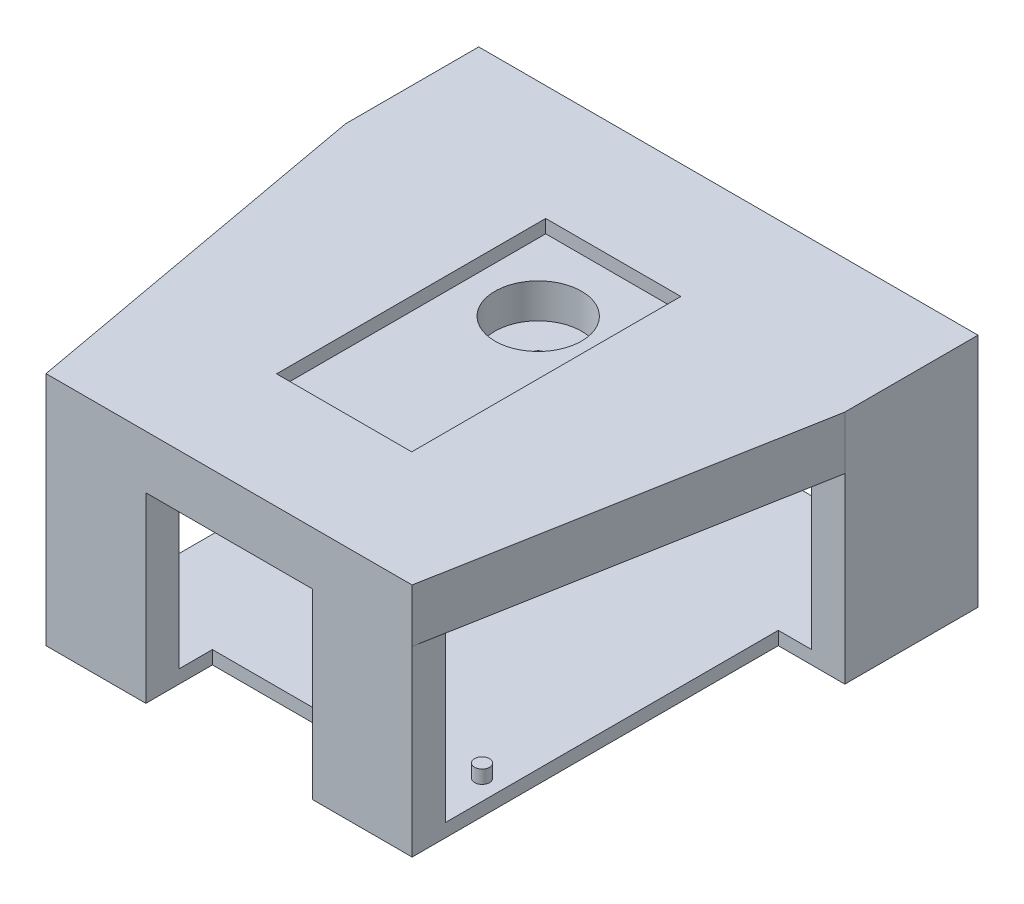
SolidWorks part; units mm, degrees
ref_plane "Front Plane" through (0, 0, 0) normal (0, 0, 1) x (1, 0, 0)
ref_plane "Top Plane" through (0, 0, 0) normal (0, 1, 0) x (1, 0, 0)
ref_plane "Right Plane" through (0, 0, 0) normal (1, 0, 0) x (0, 0, -1)
sketch "Sketch1" plane through (0, 0, 0) normal (0, 1, 0) x (1, 0, 0)
  line L1 (0, 0) -> (55, 0)
  line L2 (0, 0) -> (0, 65)
  line L3 (0, 65) -> (55, 65)
  line L4 (55, 0) -> (55, 65)
  dimension "D1" = 55
  dimension "D2" = 65
extrude "Base" add sketch "Sketch1" along normal blind 2
sketch "Sketch2" plane through (0, 2, 0) normal (0, 1, 0) x (1, 0, 0)
  line L0 (0, 0) -> (55, 0) construction
  line L2 (55, 65) -> (0, 65) construction
  circle A0 centre (3, 3.5) radius 1.125
  circle A1 centre (52, 3.5) radius 1.125
  circle A2 centre (3, 61.5) radius 1.125
  circle A3 centre (52, 61.5) radius 1.125
  point P8 (0, 0)
  point P9 (0, 0)
  point P12 (27.5, 0)
  point P13 (52, 2.848)
  dimension "D1" = 2.25
  dimension "D2" = 24.5
  dimension "D3" = 24.5
  dimension "D4" = 58
  dimension "D5" = 3.5
extrude "PiMountPegs" add sketch "Sketch2" along normal blind 2
sketch "Sketch3" plane through (0, 0, 0) normal (-1, 0, 0) x (0, 0, 1)
  line L0 (-65, 0) -> (0, 0) construction
  line L1 (-65, 2) -> (-45, 2)
  line L2 (-65, 2) -> (-65, 0)
  line L3 (-65, 0) -> (-45, 0)
  line L4 (-45, 2) -> (-45, 0)
  dimension "D1" = 20
extrude "ServoPlateLegExt-1" add sketch "Sketch3" along normal blind 10
sketch "Sketch4" plane through (55, 0, 0) normal (1, 0, 0) x (0, 0, -1)
  line L0 (0, 0) -> (65, 0) construction
  line L1 (65, 2) -> (45, 2)
  line L2 (65, 2) -> (65, 0)
  line L3 (65, 0) -> (45, 0)
  line L4 (45, 2) -> (45, 0)
  dimension "D1" = 20
extrude "ServoPlateLegExt-2" add sketch "Sketch4" along normal blind 10
sketch "Sketch5" plane through (0, 0, 0) normal (0, 0, 1) x (1, 0, 0)
  line L0 (0, 0) -> (55, 0) construction
  line L1 (0, 2) -> (15, 2)
  line L2 (0, 2) -> (0, 0)
  line L3 (0, 0) -> (15, 0)
  line L4 (15, 2) -> (15, 0)
  line L6 (55, 2) -> (40, 2)
  line L7 (55, 2) -> (55, 0)
  line L8 (55, 0) -> (40, 0)
  line L9 (40, 2) -> (40, 0)
  dimension "D1" = 15
  dimension "D2" = 15
extrude "ServoPlateLegExt-3" add sketch "Sketch5" along normal blind 10
sketch "Sketch6" plane through (0, 2, 0) normal (0, 1, 0) x (1, 0, 0)
  line L0 (-10, 45) -> (0, 45) construction
  line L1 (-10, 65) -> (-5, 65)
  line L2 (-10, 65) -> (-10, 45)
  line L3 (-10, 45) -> (-5, 45)
  line L4 (-5, 65) -> (-5, 45)
  line L5 (15, -10) -> (15, 0) construction
  line L6 (0, -10) -> (15, -10)
  line L7 (0, -10) -> (0, -5)
  line L8 (0, -5) -> (15, -5)
  line L9 (15, -10) -> (15, -5)
  line L10 (40, -10) -> (40, 0) construction
  line L11 (55, -10) -> (40, -10)
  line L12 (55, -10) -> (55, -5)
  line L13 (55, -5) -> (40, -5)
  line L14 (40, -10) -> (40, -5)
  line L15 (65, 45) -> (55, 45) construction
  line L16 (65, 65) -> (60, 65)
  line L17 (65, 65) -> (65, 45)
  line L18 (65, 45) -> (60, 45)
  line L19 (60, 65) -> (60, 45)
extrude "ServoLegs" add sketch "Sketch6" along normal blind 25.4
sketch "Sketch11" plane through (0, 27.4, 0) normal (0, 1, 0) x (1, 0, 0)
  line L0 (55, -10) -> (65, 45)
  line L1 (65, 45) -> (65, 65)
  line L2 (65, 65) -> (-10, 65)
  line L3 (-10, 65) -> (-10, 45)
  line L4 (-10, 45) -> (0, -10)
  line L5 (0, -10) -> (55, -10)
extrude "ServoPlate" add sketch "Sketch11" along normal blind 8
sketch "Sketch12" plane through (0, 35.4, 0) normal (0, 1, 0) x (1, 0, 0)
  line L0 (65, 65) -> (-10, 65) construction
  line L1 (17.35, 7.285) -> (37.65, 7.285)
  line L2 (17.35, 7.285) -> (17.35, 47.715)
  line L3 (17.35, 47.715) -> (37.65, 47.715)
  line L4 (37.65, 7.285) -> (37.65, 47.715)
  line L5 (-10, 65) -> (-10, -10) construction
  point P4 (27.5, 47.715)
  point P7 (27.5, 65)
  point P11 (17.35, 27.5)
  point P12 (-10, 27.5)
  dimension "D1" = 40.43
  dimension "D2" = 20.3
extrude "ServoSeat" cut sketch "Sketch12" against normal blind 2
sketch "Sketch13" plane through (0, 33.4, 0) normal (0, 1, 0) x (1, 0, 0)
  line L1 (37.65, 47.715) -> (17.35, 47.715) construction
  circle A0 centre (27.5, 36.44) radius 1
  point P6 (27.5, 47.715)
  dimension "D1" = 2
  dimension "D2" = 11.275
extrude "ServoScrewHole-1" cut sketch "Sketch13" against normal up to surface (6 mm away) up to face at (27.5, 27.4, -17.8571)
sketch "Sketch14" plane through (0, 33.4, 0) normal (0, 1, 0) x (1, 0, 0)
  circle A0 centre (27.5, 36.44) radius 6.5
  circle A1 centre (27.5, 36.44) radius 1 construction
  dimension "D1" = 13
extrude "ServoAxleHole" cut sketch "Sketch14" against normal blind 5.2
equation "\"PlateLegExtent\"= 10mm"
equation "\"D1@ServoPlateLegExt-1\" = \"PlateLegExtent\""
equation "\"D1@ServoPlateLegExt-3\" = \"PlateLegExtent\""
equation "\"D1@ServoPlateLegExt-2\" = \"PlateLegExtent\""
equation "\"PlateLegHeight\"= 1in"
equation "\"D1@ServoLegs\"=\"PlateLegHeight\""
equation "\"PlateThickness\"=6"
